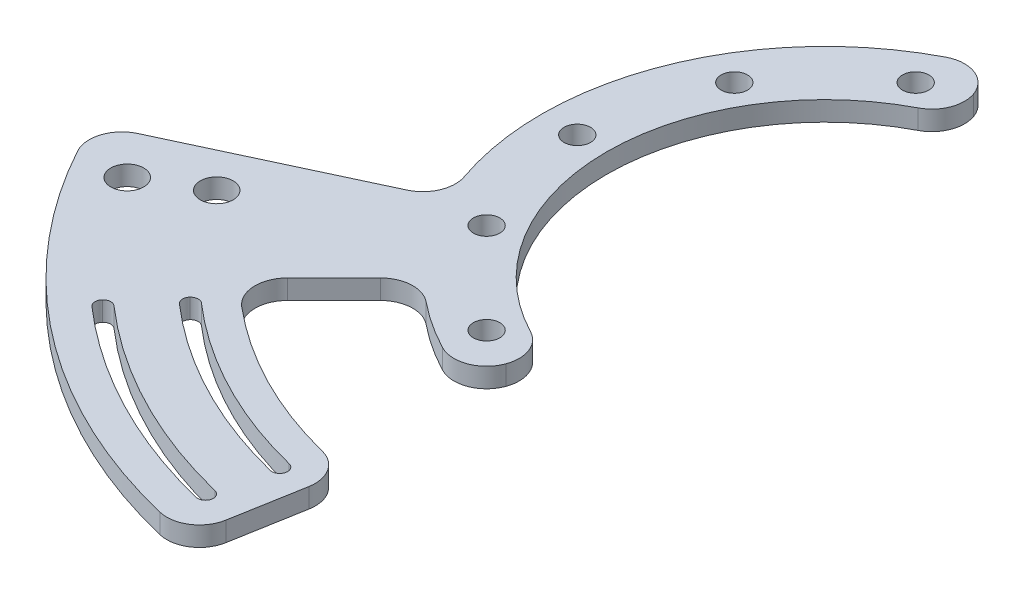
SolidWorks part; units mm, degrees
ref_plane "Front Plane" through (0, 0, 0) normal (0, 0, 1) x (1, 0, 0)
ref_plane "Top Plane" through (0, 0, 0) normal (0, 1, 0) x (1, 0, 0)
ref_plane "Right Plane" through (0, 0, 0) normal (1, 0, 0) x (0, 0, -1)
sketch "Sketch1" plane through (0, 0, 0) normal (0, 1, 0) x (1, 0, 0)
  circle A0 centre (0, 0) radius 38 construction
  circle A1 centre (0, 0) radius 43.5
  circle A2 centre (0, 0) radius 33.5
  dimension "D1" = 76
  dimension "D2" = 67
  dimension "D3" = 87
extrude "Boss-Extrude1" add sketch "Sketch1" along normal blind 3
sketch "Sketch3" plane through (0, 3, 0) normal (0, 1, 0) x (1, 0, 0)
  line L0 (0, 0) -> (-38, 0) construction
  circle A0 centre (-38, 0) radius 2.025
  dimension "D1" = 4.05
  dimension "D2" = 38
extrude "Cut-Extrude2" cut sketch "Sketch3" against normal through all both and the other way through all
pattern_circular "CirPattern1" count 12 over 360 about axis through (0, 3, 0) along (0, 1, 0) of "Cut-Extrude2"
sketch "Sketch2" plane through (0, 3, 0) normal (0, 1, 0) x (1, 0, 0)
  line L0 (0, 0) -> (43.5, 0)
  line L1 (0, 0) -> (-14.8779, -40.8766)
  circle A0 centre (0, 0) radius 43.5 construction
  arc A1 (-14.8779, -40.8766) -> (43.5, 0) centre (0, 0) ccw
  dimension "D1" = 110
extrude "Cut-Extrude1" cut sketch "Sketch2" against normal through all both and the other way through all
mirror "Mirror1" about plane through (0, 0, 0) normal (0, 0, 1) of "Cut-Extrude1"
sketch "Sketch4" plane through (0, 0, 0) normal (0, 1, 0) x (1, 0, 0)
  line L0 (0, 0) -> (-43.5, 0) construction
  line L1 (0, 0) -> (-76.583, -35.7112)
  line L2 (-14.6733, -83.2163) -> (-11.0267, -62.5353)
  line L3 (-57.5505, -26.8363) -> (-76.583, -35.7112)
  line L4 (-44.9013, -44.9013) -> (-30.7591, -30.7591)
  arc A0 (-14.8779, 40.8766) -> (-14.8779, -40.8766) centre (0, 0) ccw construction
  arc A1 (-76.583, -35.7112) -> (-14.6733, -83.2163) centre (0, 0) ccw
  arc A2 (-11.0267, -62.5353) -> (-57.5505, -26.8363) centre (0, 0) cw construction
  arc A3 (-11.0267, -62.5353) -> (-44.9013, -44.9013) centre (0, 0) cw
  arc A4 (-30.7591, -30.7591) -> (-39.4244, -18.3839) centre (0, 0) cw
  dimension "D5" = 45
  dimension "D1" = 21
  dimension "D2" = 63.5
  dimension "D3" = 25
  dimension "D4" = 80
extrude "Boss-Extrude2" add sketch "Sketch4" along normal up to surface (3 mm away) contours L4 L1 A1 L2 region at (-43.7257, 0, 51.6581) up to face at (-38, 3, 2.025)
sketch "Sketch5" plane through (0, 3, 0) normal (0, 1, 0) x (1, 0, 0)
  line L0 (-17.6587, -76.4881) -> (-15.5216, -67.2315) construction
  line L1 (-52.5268, -58.3369) -> (-46.17, -51.277) construction
  line L2 (-14.6733, -83.2163) -> (-11.0267, -62.5353) construction
  line L3 (-39.4244, -18.3839) -> (-76.583, -35.7112) construction
  arc A0 (-46.17, -51.277) -> (-15.5216, -67.2315) centre (0, 0) ccw
  arc A1 (-52.5268, -58.3369) -> (-17.6587, -76.4881) centre (0, 0) ccw
  arc A2 (-44.9013, -44.9013) -> (-11.0267, -62.5353) centre (0, 0) ccw construction
  dimension "D4" = 5.5
  dimension "D1" = 9.5
  dimension "D2" = 3
  dimension "D3" = 23
extrude "Cut-Extrude-Thin1" cut sketch "Sketch5" against normal blind 3 thin thin type mid plane wall 2.4
fillet "Fillet1" radius 1.2 8 edges at (-46.973, 1.5, 52.1688) (-53.3297, 1.5, 59.2286) (-45.3671, 1.5, 50.3852) (-51.7238, 1.5, 57.4451) (-15.2517, 1.5, 66.0623) (-17.3887, 1.5, 75.3188) (-15.7916, 1.5, 68.4008) (-17.9286, 1.5, 77.6573)
fillet "Fillet2" radius 5 10 edges at (-11.4577, 1.5, -31.4797) (-11.4577, 1.5, 31.4797) (-39.4244, 1.5, 18.3839) (-76.583, 1.5, 35.7112) (-14.6733, 1.5, 83.2163) (-11.0267, 1.5, 62.5353) (-30.7591, 1.5, 30.7591) (-44.9013, 1.5, 44.9013)
sketch "Sketch6" plane through (0, 3, 0) normal (0, 1, 0) x (1, 0, 0)
  line L0 (0, 0) -> (-72.4306, -43.5207) construction
  line L1 (-43.7217, -20.3878) -> (-71.9088, -33.5316) construction
  arc A0 (-74.1854, -40.4571) -> (-19.8779, -82.1287) centre (0, 0) ccw construction
  circle A1 centre (-58.2874, -35.0226) radius 2.525
  circle A2 centre (-66.859, -40.173) radius 2.525
  dimension "D1" = 5.05
  dimension "D2" = 10
  dimension "D3" = 78
  dimension "D4" = 6
extrude "Cut-Extrude3" cut sketch "Sketch6" against normal through all both and the other way through all
sketch "Sketch7" plane through (0, 0, 0) normal (0, 1, 0) x (1, 0, 0)
  line L0 (0, 0) -> (-58.9789, 41.2975) construction
  line L1 (-58.9789, 41.2975) -> (-35.6331, 24.9506)
  line L2 (0, 0) -> (-43.5, 0) construction
  line L3 (-58.9789, 31.2975) -> (-39.6941, 17.7941)
  line L5 (-58.9789, 41.2975) -> (-58.9789, 31.2975)
  line L8 (-58.9789, 41.2975) -> (-73.9789, 41.2975)
  line L9 (-58.9789, 41.2975) -> (-58.9789, 31.2975)
  line L10 (-73.9789, 41.2975) -> (-73.9789, 31.2975)
  line L11 (-58.9789, 31.2975) -> (-73.9789, 31.2975)
  arc A0 (-20.0605, 38.5983) -> (-41.1096, -14.2216) centre (0, 0) ccw construction
  arc A1 (-39.6941, 17.7941) -> (-35.6331, 24.9506) centre (0, 0) cw
  dimension "D1" = 72
  dimension "D2" = 35
  dimension "D3" = 10
  dimension "D4" = 15
extrude "Boss-Extrude3" [suppressed] add sketch "Sketch7" along normal up to surface (3 mm away)
sketch "Sketch9" [suppressed] plane through (0, 3, 0) normal (0, 1, 0) x (1, 0, 0)
  line L0 (-73.9789, 37.2975) -> (-53.2664, 37.2975) construction
  line L1 (-73.9789, 41.2975) -> (-73.9789, 31.2975) construction
  line L2 (-58.9789, 41.2975) -> (-35.6331, 24.9506) construction
  line L3 (-58.9789, 41.2975) -> (-73.9789, 41.2975) construction
  circle A0 centre (-69.9789, 37.2975) radius 1.2
  circle A1 centre (-60.4789, 37.2975) radius 1.2
  dimension "D1" = 2.4
  dimension "D2" = 9.5
  dimension "D3" = 4
  dimension "D4" = 4
extrude "Cut-Extrude5" [suppressed] cut sketch "Sketch9" against normal through all both and the other way through all
